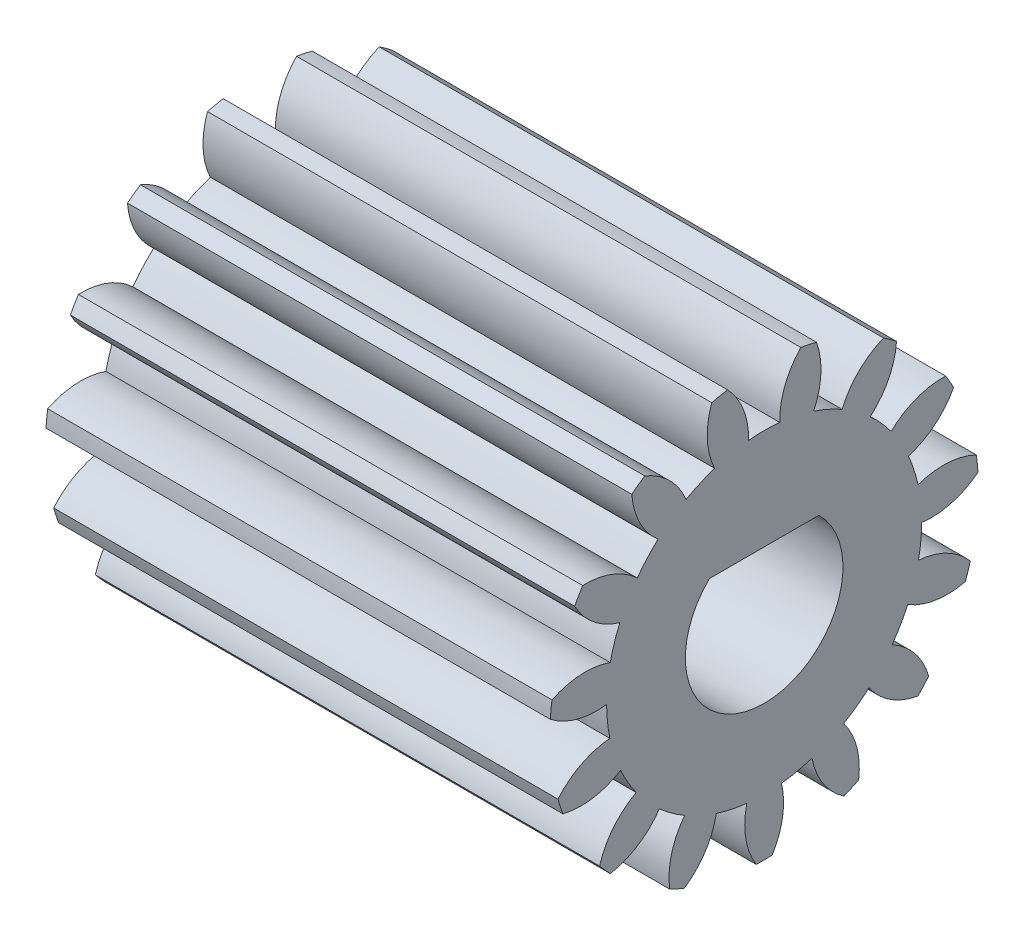
SolidWorks part; units mm, degrees
ref_plane "Plane1" through (0, 0, 0) normal (0, 0, 1) x (1, 0, 0)
ref_plane "Plane2" through (0, 0, 0) normal (0, 1, 0) x (1, 0, 0)
ref_plane "Plane3" through (0, 0, 0) normal (1, 0, 0) x (0, 0, -1)
sketch "HoldingSke" plane through (0, 0, 0) normal (0, 1, 0) x (1, 0, 0)
  line L0 (0, 0) -> (1.2074, -0.3235)
  line L1 (-15, 0) -> (100, 0) construction
  line L2 (0, 0) -> (-2.1039, 2.3779)
  line L3 (0, 0) -> (-11.863, 4.5341)
  line L4 (0, 0) -> (8.3417, 2.2352)
  line L5 (0, 0) -> (-46.8476, -17.4728)
  line L6 (0, 0) -> (-13.2634, -8.9489)
  line L7 (-2.1039, 2.3779) -> (8.6587, 51.2063)
  line L8 (-76.2, 54.61) -> (-75.5, 54.61)
  line L9 (-67.7845, 28.3722) -> (-49.3413, 33.142)
  line L10 (-76.2, 71.12) -> (104.1128, 71.12)
  line L11 (0, 0) -> (-16, 0)
  line L12 (-76.2, 101.6) -> (-76.17, 101.6)
  line L13 (24.9733, 27.94) -> (52.9518, 28.4284)
  line L14 (24.9733, 27.94) -> (24.9743, 27.94)
  line L15 (24.9733, 27.94) -> (100.4006, 29.5858)
  line L16 (-63.627, -0.8) -> (-12.827, -0.8)
  circle A0 centre (0, 0) radius 2
  circle A1 centre (0, 0) radius 4.999
  circle A2 centre (0, 0) radius 37.5
  circle A3 centre (0, 0) radius 2
  dimension "Num_teeth" = 15
  dimension "Pitch_radius" = 180.3128
  dimension "Width" = 16
  dimension "Thickness" = 16
sketch "BasProSke" plane through (0, 0, 0) normal (0, 1, 0) x (1, 0, 0)
  line L0 (-10, 0) -> (60, 0) construction
  line L1 (0, 0) -> (0, 6.8)
  line L2 (0, 0) -> (16, 0)
  line L3 (16, 0) -> (16, 6.8)
  line L4 (16, 6.8) -> (0, 6.8)
  dimension "Thickness" = 16
  dimension "Diameter" = 13.6
revolve "Base-Revolve" add sketch "BasProSke" angle 360 about L0
sketch "TooCutSke" plane through (0, 0, 0) normal (1, 0, 0) x (0, 0, -1)
  line L1 (0, 0) -> (0, 107) construction
  line L2 (0, 0) -> (-0.6796, 5.9614) construction
  line L3 (0, 0) -> (-2.4835, 11.6838) construction
  line L4 (-0.6796, 5.9614) -> (-1.2417, 5.8419) construction
  arc A0 (0.4951, 4.9744) -> (-0.4951, 4.9744) centre (0, 0) ccw
  arc A1 (1.1854, 6.7217) -> (-1.1854, 6.7217) centre (0, 0) ccw
  circle A2 centre (0, 0) radius 6 construction
  circle A3 centre (0, 0) radius 5.8089 construction
  arc A4 (-0.4951, 4.9744) -> (-1.1854, 6.7217) centre (-2.8943, 5.0365) ccw
  arc A5 (1.1854, 6.7217) -> (0.4951, 4.9744) centre (2.8943, 5.0365) ccw
extrude "ToothCut" cut sketch "TooCutSke" along normal through all
fillet "Breaks" [suppressed] radius 0.016 tangent propagation no
fillet "RootFillets" [suppressed] radius 0.201
pattern_circular "TeethCuts" count 15 every 24 about axis through (-10, 0, 0) along (1, 0, 0) of "ToothCut", "RootFillets", "Breaks"
sketch "HubNeaOneSke" plane through (0, 0, 0) normal (-1, 0, 0) x (0, 0, 1)
  circle A0 centre (0, 0) radius 4.999
  dimension "Diameter" = 9.998
extrude "HubNearOne" [suppressed] add sketch "HubNeaOneSke" along normal blind 34.0005
sketch "HubNeaBotSke" plane through (0, 0, 0) normal (-1, 0, 0) x (0, 0, 1)
  circle A0 centre (0, 0) radius 4.999
  dimension "Diameter" = 9.998
extrude "HubNearBoth" [suppressed] add sketch "HubNeaBotSke" along normal blind 17.0003
ref_plane "FarPln" through (16, 0, 0) normal (1, 0, 0) x (0, 0, -1)
sketch "HubFarSke" plane through (16, 0, 0) normal (1, 0, 0) x (0, 0, -1)
  circle A0 centre (0, 0) radius 4.999
  dimension "Diameter" = 9.998
extrude "HubFar" [suppressed] add sketch "HubFarSke" along normal blind 17.0003
sketch "BorSke" plane through (0, 0, 0) normal (1, 0, 0) x (0, 0, -1)
  circle A0 centre (0, 0) radius 2
  dimension "Diameter" = 4
extrude "Bore" cut sketch "BorSke" along normal mid plane 100.001
sketch "KeySke" plane through (0, 0, 0) normal (1, 0, 0) x (0, 0, -1)
  line L0 (-0.8, 0) -> (-0.8, 2.7)
  line L1 (-0.8, 2.7) -> (0.8, 2.7)
  line L2 (0.8, 2.7) -> (0.8, 0)
  line L3 (0, 0) -> (0, 34) construction
  line L4 (-0.8, 0) -> (0.8, 0)
extrude "Keyway" [suppressed] cut sketch "KeySke" along normal mid plane 100.001
pattern_circular "Keyway2" [suppressed] count 2 every 90 about axis through (-10, 0, 0) along (1, 0, 0) reverse direction yes
sketch "Sketch1" plane through (16, 0, 0) normal (1, 0, 0) x (0, 0, -1)
  line L0 (1.7349, 1.8) -> (-1.7349, 1.8)
  circle A0 centre (0, 0) radius 2.5
  dimension "D1" = 5
  dimension "D2" = 1.8
extrude "Boss-Extrude1" add sketch "Sketch1" against normal through all contours L0 A0 region at (16, 2.0837, 0)
extrude "Cut-Extrude1" cut sketch "Sketch1<3>" against normal through all contours L0 A0 region at (16, -0.1938, 0)
sketch "Sketch1<3>" plane through (16, 0, 0) normal (1, 0, 0) x (0, 0, -1) same geometry as "Sketch1"
equation "' \"Module@HoldingSke\" = 6.35"
equation "' \"Num_teeth@HoldingSke\" = 12"
equation "' \"Ap@HoldingSke\" =  20"
equation "' \"Ap@HoldingSke\" = 20"
equation "' \"Width@HoldingSke\" = 0.5 * 25.4"
equation "' \"Hub_dia@HoldingSke\"= 1 * 25.4"
equation "' \"Hub_dia@HoldingSke\" = 1 * 25.4"
equation "' \"Overall_len@HoldingSke\" = 1.0 * 25.4"
equation "' \"Bore@HoldingSke\" = 0.75 * 25.4"
equation "' \"T_dim@HoldingSke\" = 0.1 * 25.4"
equation "' \"Width@KeySke\" = 0.25 * 25.4"
equation "' \"Show_teeth@HoldingSke\" = 13"
equation "' \"Backlash@HoldingSke\" = 0.009 * 25.4"
equation "' \"Addendum_fac@HoldingSke\" = 1.0"
equation "' \"Dedendum_fac@HoldingSke\" = 1.25"
equation "' \"Dedendum_add@HoldingSke\" = 0.00005 * 25.4"
equation "' \"Clearance_fac@HoldingSke\" = 0.25"
equation "\"Pitch@HoldingSke\" = 1 / \"Module@HoldingSke\""
equation "\"Overcut_dia@TooCutSke\" = (\"Num_teeth@HoldingSke\" + 2 * \"Addendum_fac@HoldingSke\") / \"Pitch@HoldingSke\" + 0.002 * 25.4"
equation "\"Pitch_dia@TooCutSke\" = \"Num_teeth@HoldingSke\" / \"Pitch@HoldingSke\""
equation "\"Base_dia@TooCutSke\" = \"Num_teeth@HoldingSke\" / \"Pitch@HoldingSke\" * cos((\"Ap@HoldingSke\"  * 3.14159265 / 180))"
equation "\"Root_dia@TooCutSke\" = (\"Num_teeth@HoldingSke\" + 2) / \"Pitch@HoldingSke\" - 2 * (\"Addendum_fac@HoldingSke\" + \"Dedendum_fac@HoldingSke\") / \"Pitch@HoldingSke\" - \"Dedendum_add@HoldingSke\" * 2"
equation "\"Half_ang@TooCutSke\" = 180 / \"Num_teeth@HoldingSke\""
equation "\"Half_CT@TooCutSke\" = \"Num_teeth@HoldingSke\" / \"Pitch@HoldingSke\" * sin((3.14159265 / 2 / \"Num_teeth@HoldingSke\")) / 2 - 7 * \"Backlash@HoldingSke\" / 4"
equation "\"Flank_rad@TooCutSke\" = \"Num_teeth@HoldingSke\" / \"Pitch@HoldingSke\" / 5"
equation "\"Radius@RootFillets\" = \"Clearance_fac@HoldingSke\" / \"Pitch@HoldingSke\" + \"Dedendum_add@HoldingSke\""
equation "\"Break_rad@Breaks\" = 0.02 / \"Pitch@HoldingSke\""
equation "\"Thickness@HoldingSke\" = \"Width@HoldingSke\""
equation "\"OAL@HoldingSke\" = \"Thickness@HoldingSke\""
equation "\"MHD@HoldingSke\" = (\"Num_teeth@HoldingSke\" + 2) / \"Pitch@HoldingSke\" - 2 * (\"Addendum_fac@HoldingSke\" + \"Dedendum_fac@HoldingSke\")  / \"Pitch@HoldingSke\" - \"Dedendum_add@HoldingSke\" * 2"
equation "\"MBD@HoldingSke\" = (\"Num_teeth@HoldingSke\" + 2) / \"Pitch@HoldingSke\" - 2 * (\"Addendum_fac@HoldingSke\" + \"Dedendum_fac@HoldingSke\")  / \"Pitch@HoldingSke\" - \"Dedendum_add@HoldingSke\" * 2 - 0.002 * 25.4"
equation "\"MHD@HoldingSke\" = ((sgn( \"MHD@HoldingSke\" - \"Hub_dia@HoldingSke\" )-1)*( \"MHD@HoldingSke\" - \"Hub_dia@HoldingSke\" ))/-2+ \"Hub_dia@HoldingSke\""
equation "\"MBD@HoldingSke\" = ((sgn( \"MBD@HoldingSke\" - \"Bore@HoldingSke\" )-1)*( \"MBD@HoldingSke\" - \"Bore@HoldingSke\" ))/-2+ \"Bore@HoldingSke\""
equation "\"OAL@HoldingSke\" = ((sgn( \"OAL@HoldingSke\" - \"Overall_len@HoldingSke\" )+1)*( \"OAL@HoldingSke\" - \"Overall_len@HoldingSke\" ))/2 + \"Overall_len@HoldingSke\" + 0.000002 * 25.4"
equation "\"Num_teeth@TeethCuts\" = int( \"Show_teeth@HoldingSke\" ) + 1"
equation "\"Num_teeth@TeethCuts\" = ((sgn( \"Num_teeth@TeethCuts\" - \"Num_teeth@HoldingSke\" )-1)*( \"Num_teeth@TeethCuts\" - \"Num_teeth@HoldingSke\" ))/-2+ \"Num_teeth@HoldingSke\""
equation "\"Num_teeth@TeethCuts\" = ((sgn( \"Num_teeth@TeethCuts\" - 2.0)+1)*( \"Num_teeth@TeethCuts\" - 2.0))/2 +2.0"
equation "\"Angle@TeethCuts\" = 360.0 / \"Num_teeth@HoldingSke\""
equation "\"Diameter@BasProSke\" = (\"Num_teeth@HoldingSke\" + 2 * \"Addendum_fac@HoldingSke\") / \"Pitch@HoldingSke\""
equation "\"Thickness@BasProSke\"  = \"Thickness@HoldingSke\""
equation "' \"Fillet_rad@BasProSke\" =  \"Thickness@HoldingSke\" * 0.05"
equation "' \"Fillet_rad@BasProSke\" = \"Thickness@HoldingSke\" * 0.05"
equation "\"MHD@HoldingSke\" = ((sgn( \"MHD@HoldingSke\" - \"Root_dia@TooCutSke\" )-1)*( \"MHD@HoldingSke\" - \"Root_dia@TooCutSke\" ))/-2+ \"Root_dia@TooCutSke\""
equation "\"Diameter@HubNeaOneSke\" = \"MHD@HoldingSke\""
equation "\"Length@HubNearOne\" = \"OAL@HoldingSke\" - \"Thickness@BasProSke\""
equation "\"Diameter@HubNeaBotSke\" = \"MHD@HoldingSke\""
equation "\"Length@HubNearBoth\" = ( \"OAL@HoldingSke\" - \"Thickness@BasProSke\" ) / 2.0"
equation "\"Thickness@FarPln\" = \"Thickness@BasProSke\""
equation "\"Diameter@HubFarSke\" = \"MHD@HoldingSke\""
equation "\"Length@HubFar\" = ( \"OAL@HoldingSke\" - \"Thickness@BasProSke\" ) / 2.0"
equation "\"Diameter@BorSke\" = \"MBD@HoldingSke\""
equation "\"D1@Bore\" = \"OAL@HoldingSke\" * 2.0"
equation "\"D1@Keyway\" = \"OAL@HoldingSke\" * 2.0"
equation "\"Offset@KeySke\" = \"T_dim@HoldingSke\" + \"MBD@HoldingSke\" / 2.0"
equation "\"D2@Sketch1\"=4.3-2.5"
